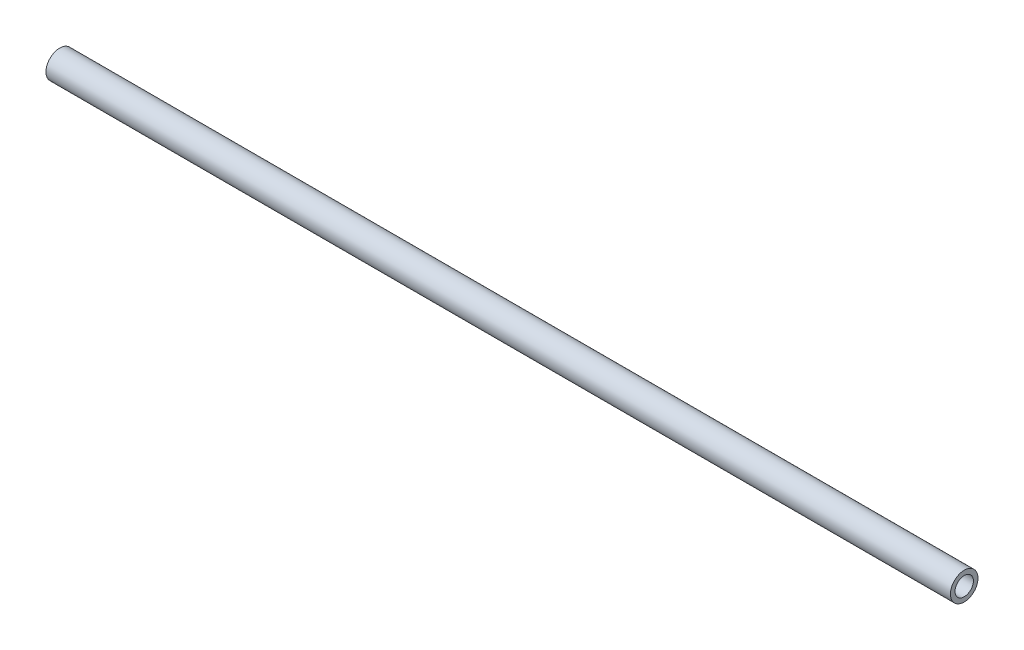
SolidWorks part; units mm, degrees
material "NEOPRENE"
ref_plane "Front Plane" through (0, 0, 0) normal (0, 0, 1) x (1, 0, 0)
ref_plane "Top Plane" through (0, 0, 0) normal (0, 1, 0) x (1, 0, 0)
ref_plane "Right Plane" through (0, 0, 0) normal (1, 0, 0) x (0, 0, -1)
sketch "Sketch1" plane through (0, 0, 0) normal (1, 0, 0) x (0, 0, -1)
  circle A0 centre (0, 0) radius 6.35
  circle A1 centre (0, 0) radius 9.525
  dimension "D1" = 12.7
  dimension "D2" = 19.05
extrude "Boss-Extrude1" add sketch "Sketch1" along normal blind 625.348
